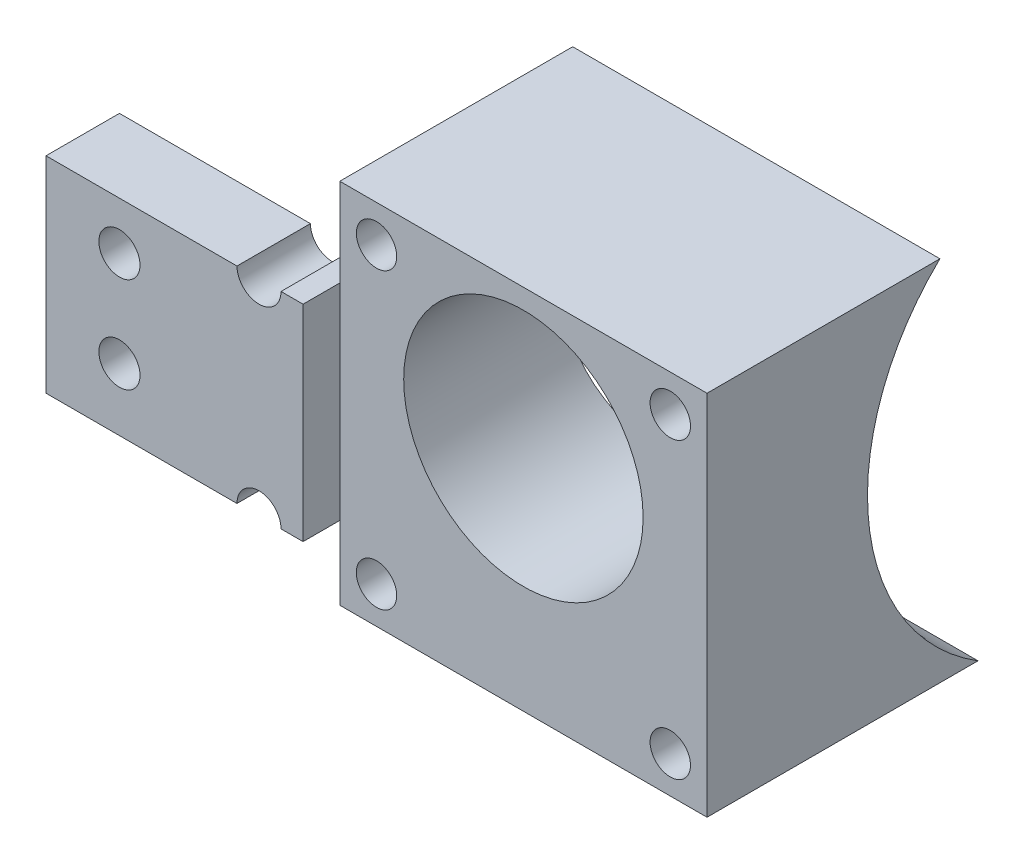
SolidWorks part; units mm, degrees
ref_plane "Front Plane" through (0, 0, 0) normal (0, 0, 1) x (1, 0, 0)
ref_plane "Top Plane" through (0, 0, 0) normal (0, 1, 0) x (1, 0, 0)
ref_plane "Right Plane" through (0, 0, 0) normal (1, 0, 0) x (0, 0, -1)
sketch "Sketch1" plane through (0, 0, 0) normal (0, 0, 1) x (1, 0, 0)
  line L0 (0, -2) -> (0, 4) construction
  line L1 (-25, 23) -> (25, 23)
  line L2 (-25, 23) -> (-25, -27)
  line L3 (-25, -27) -> (25, -27)
  line L4 (25, 23) -> (25, -27)
  line L5 (-25, 23) -> (25, -27) construction
  line L6 (-25, -27) -> (25, 23) construction
  circle A1 centre (-20, 18) radius 2.75
  circle A2 centre (20, 18) radius 2.75
  circle A3 centre (20, -22) radius 2.75
  circle A4 centre (-20, -22) radius 2.75
  circle A5 centre (0, 4) radius 16.3
  point P0 (0, -2)
  dimension "D6" = 5.5
  dimension "D8" = 6
  dimension "D11" = 32.6
  dimension "D1" = 2
  dimension "D2" = 50
  dimension "D3" = 50
  dimension "D5" = 20
  dimension "D7" = 20
  dimension "D9" = 20
  dimension "D10" = 20
extrude "Boss-Extrude1" add sketch "Sketch1" along normal blind 53.6
sketch "Sketch2" plane through (0, 0, 0) normal (1, 0, 0) x (0, 0, -1)
  circle A0 centre (0, 0) radius 31.75
  dimension "D1" = 63.5
extrude "Cut-Extrude1" cut sketch "Sketch2" against normal through all and the other way through all
sketch "Sketch3" plane through (-25, 0, 0) normal (-1, 0, 0) x (0, 0, 1)
  line L3 (53.6, 23) -> (21.8875, 23)
  line L4 (16.7052, -27) -> (53.6, -27)
  line L5 (53.6, -27) -> (53.6, 23)
  line L6 (53.6, 23) -> (21.8875, 23)
  line L7 (16.7052, -27) -> (53.6, -27)
  line L8 (53.6, -27) -> (53.6, 23)
  arc A1 (16.7052, -27) -> (21.8875, 23) centre (0, 0) ccw
  arc A2 (16.7052, -27) -> (21.8875, 23) centre (0, 0) ccw
  dimension "D1" = 0
sketch "Sketch4" plane through (25, 0, 0) normal (1, 0, 0) x (0, 0, -1)
  line L3 (-53.6, -27) -> (-16.7052, -27)
  line L4 (-21.8875, 23) -> (-53.6, 23)
  line L5 (-53.6, 23) -> (-53.6, -27)
  line L8 (-53.6, 11) -> (-53.6, -17)
  line L12 (-53.6, 11) -> (-29.7836, 11)
  line L13 (-53.6, 23) -> (-21.8875, 23) construction
  line L14 (0, 0) -> (-85.4701, 0) construction
  line L15 (-53.6, -11) -> (-29.7836, -11) construction
  line L16 (-53.6, -17) -> (-26.8153, -17)
  arc A0 (-21.8875, 23) -> (-16.7052, -27) centre (0, 0) ccw construction
  arc A1 (-21.8875, 23) -> (-16.7052, -27) centre (0, 0) ccw
  arc A2 (-29.7836, 11) -> (-26.8153, -17) centre (0, 0) ccw
  dimension "D3" = 12
  dimension "D4" = 6
  dimension "D1" = 0
extrude "Boss-Extrude3" add sketch "Sketch4" along normal blind 35
sketch "Sketch12" plane through (0, 0, 53.6) normal (0, 0, 1) x (1, 0, 0)
  line L6 (60, 11) -> (60, -17) construction
  line L7 (60, 11) -> (25, 11) construction
  line L8 (60, -17) -> (25, -17) construction
  line L9 (60, 11) -> (60, -17)
  line L10 (60, 11) -> (25, 11)
  line L11 (60, -17) -> (25, -17)
  line L12 (25, 11) -> (25, -17)
sketch "Sketch9" plane through (0, 0, 0) normal (0, 0, 1) x (1, 0, 0)
  line L0 (31, 11) -> (31, -17) construction
  line L3 (25, -27) -> (25, -17) construction
  circle A4 centre (31, 11) radius 3
  circle A5 centre (31, -17) radius 3
  dimension "D1" = 6
  dimension "D2" = 6
extrude "Cut-Extrude5" cut sketch "Sketch9" against normal through all both and the other way through all
sketch "Sketch10" plane through (0, 0, 53.6) normal (0, 0, 1) x (1, 0, 0)
  line L0 (50, 4.5) -> (50, -8.5) construction
  line L1 (60, -2) -> (0, -2) construction
  line L2 (60, 11) -> (60, -17) construction
  line L3 (25, -27) -> (25, -17) construction
  line L4 (60, 11) -> (60, -17) construction
  line L5 (50, 22) -> (50, -27) construction
  line L6 (-25, -27) -> (25, -27) construction
  circle A0 centre (50, 4.5) radius 2.8
  circle A1 centre (50, -8.5) radius 2.8
  point P7 (60, -3)
  point P8 (50, -2)
  dimension "D1" = 5.6
  dimension "D2" = 1
  dimension "D3" = 13
  dimension "D4" = 25
extrude "Cut-Extrude6" cut sketch "Sketch10" against normal blind 10 and the other way through all
ref_plane "Plane1" through (0, 0, 0) normal (1, 0, 0) x (0, 0, -1)
sketch "Sketch13" plane through (0, 0, 53.6) normal (0, 0, 1) x (1, 0, 0)
  line L12 (60, 11) -> (60, -17) construction
  line L13 (60, 11) -> (25, 11) construction
  line L14 (25, 11) -> (25, -17) construction
  line L15 (60, -17) -> (25, -17) construction
  line L16 (60, 11) -> (60, -17)
  line L17 (60, 11) -> (34, 11)
  line L18 (25, 11) -> (25, -17)
  line L19 (60, -17) -> (34, -17)
  line L20 (28, 11) -> (25, 11)
  line L21 (28, -17) -> (25, -17)
  arc A4 (28, 11) -> (34, 11) centre (31, 11) ccw construction
  arc A5 (34, -17) -> (28, -17) centre (31, -17) ccw construction
  circle A6 centre (50, 4.5) radius 2.8 construction
  circle A7 centre (50, -8.5) radius 2.8 construction
  arc A8 (28, 11) -> (34, 11) centre (31, 11) ccw
  arc A9 (34, -17) -> (28, -17) centre (31, -17) ccw
  circle A10 centre (50, 4.5) radius 2.8
  circle A11 centre (50, -8.5) radius 2.8
  circle M34 centre (50, 4.5) radius 2.8
  circle M35 centre (50, -8.5) radius 2.8
  line M38 (60, 11) -> (34, 11)
  arc M39 (34, 11) -> (28, 11) centre (31, 11) cw
  line M40 (28, 11) -> (25, 11)
  line M46 (25, -17) -> (28, -17)
  arc M47 (28, -17) -> (34, -17) centre (31, -17) cw
  line M48 (34, -17) -> (60, -17)
  line M49 (60, -17) -> (60, 11)
extrude "Cut-Extrude8" cut sketch "Sketch13" against normal through all from offset 5 contours M34 | M35 | L18 M40 M46 M47 M48 M49 M38 M39 M34 M35 region at (42.4509, -3.0546, 53.6) region at (50, 4.5, 53.6) region at (50, -8.5, 53.6) offset against normal yes
extrude "Boss-Extrude4" add sketch "Sketch13<3>" along normal blind 5
sketch "Sketch13<3>" plane through (0, 0, 53.6) normal (0, 0, 1) x (1, 0, 0) same geometry as "Sketch13"
mirror "Mirror3" about plane through (0, 0, 0) normal (1, 0, 0) of "Cut-Extrude8", "Cut-Extrude5", "Boss-Extrude3", "Boss-Extrude4"
extrude "Cut-Extrude9" cut sketch "Sketch13<4>" along normal blind 5 and the other way blind 5
sketch "Sketch13<4>" plane through (0, 0, 53.6) normal (0, 0, 1) x (1, 0, 0) same geometry as "Sketch13"
